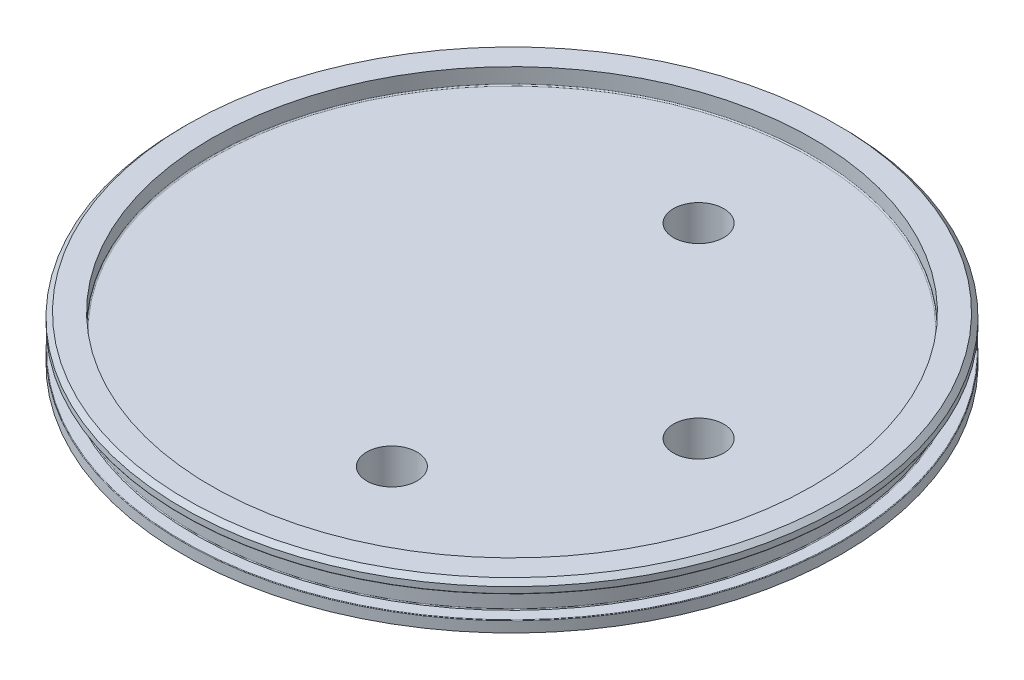
SolidWorks part; units mm, degrees
material "6061-T6 (SS)"
ref_plane "Front Plane" through (0, 0, 0) normal (0, 0, 1) x (1, 0, 0)
ref_plane "Top Plane" through (0, 0, 0) normal (0, 1, 0) x (1, 0, 0)
ref_plane "Right Plane" through (0, 0, 0) normal (1, 0, 0) x (0, 0, -1)
sketch "Sketch1" plane through (0, 0, 0) normal (0, 0, 1) x (1, 0, 0)
  line L0 (0, 48.1922) -> (0, -25.6743) construction
  line L1 (0, 0) -> (72.898, 0)
  line L2 (72.898, 0) -> (72.898, 2.4638)
  line L3 (72.898, 2.4638) -> (70.0532, 2.4638)
  line L4 (70.0532, 2.4638) -> (70.0532, 7.4422)
  line L5 (70.0532, 7.4422) -> (72.898, 7.4422)
  line L6 (72.898, 7.4422) -> (72.898, 9.906)
  line L7 (72.898, 9.906) -> (66.548, 9.906)
  line L8 (66.548, 9.906) -> (66.548, 6.35)
  line L9 (66.548, 6.35) -> (0, 6.35)
  line L10 (0, 6.35) -> (0, 0)
  dimension "D1" = 145.796
  dimension "D2" = 4.9784
  dimension "D3" = 2.8448
  dimension "D4" = 9.906
  dimension "D5" = 6.35
  dimension "D6" = 6.35
revolve "Revolve1" add sketch "Sketch1" angle 360 about L0
sketch "Sketch6" plane through (0, 0, 0) normal (0, -1, 0) x (1, 0, 0)
  circle A0 centre (0, 0) radius 66.04
  dimension "D1" = 132.08
extrude "Boss-Extrude1" add sketch "Sketch6" along normal blind 2.54
hole_wizard "Pipe Tap Drill for 1/4 Tap - GN2" positions "Sketch2" profile "Sketch3" hole size "1/4" standard "ANSI Inch" end condition through all
sketch "Sketch2" plane through (0, 6.35, 0) normal (0, 1, 0) x (1, 0, 0)
  line L3 (0, 41.275) -> (0, 0) construction
  line L4 (0, 0) -> (41.275, 0) construction
  line L6 (0, 0) -> (12.7, -39.2726) construction
  point P41 (12.7, -39.2726)
  point P44 (0, 41.275)
  point P47 (41.275, 0)
  point P61 (33.02, -24.765)
  dimension "D1" = 41.275
  dimension "D2" = 41.275
  dimension "D3" = 41.275
  dimension "D4" = 12.7
sketch "Sketch3" plane through (12.7, 6.35, 39.2726) normal (1, 0, 0) x (0, 0, 1)
  line L0 (0, 0) -> (0, 8.89)
  line L1 (0, 8.89) -> (5.5626, 8.89)
  line L2 (5.5626, 8.89) -> (5.5626, 0)
  line L5 (5.5626, 0) -> (0, 0)
  line L11 (0, -6.35) -> (0, 107.95) construction
  dimension "Thru Hole Dia." = 11.1252
  dimension "Thru Hole Depth" = 8.89
fillet "CNC ID Fillet" radius 0.1778 3 edges at (-70.0532, 7.4422, 0) (-70.0532, 2.4638, 0) (66.04, 0, 0)
fillet "CNC OD Fillet" radius 0.127 3 edges at (-72.898, 7.4422, 0) (-72.898, 2.4638, 0) (66.04, -2.54, 0)
chamfer "CNC Chamfers" distance 1.016 angle 45 1 edges at (-72.898, 9.906, 0)
fillet "CNC Bore Fillet" radius 0.254 1 edges at (-66.548, 6.35, 0)
